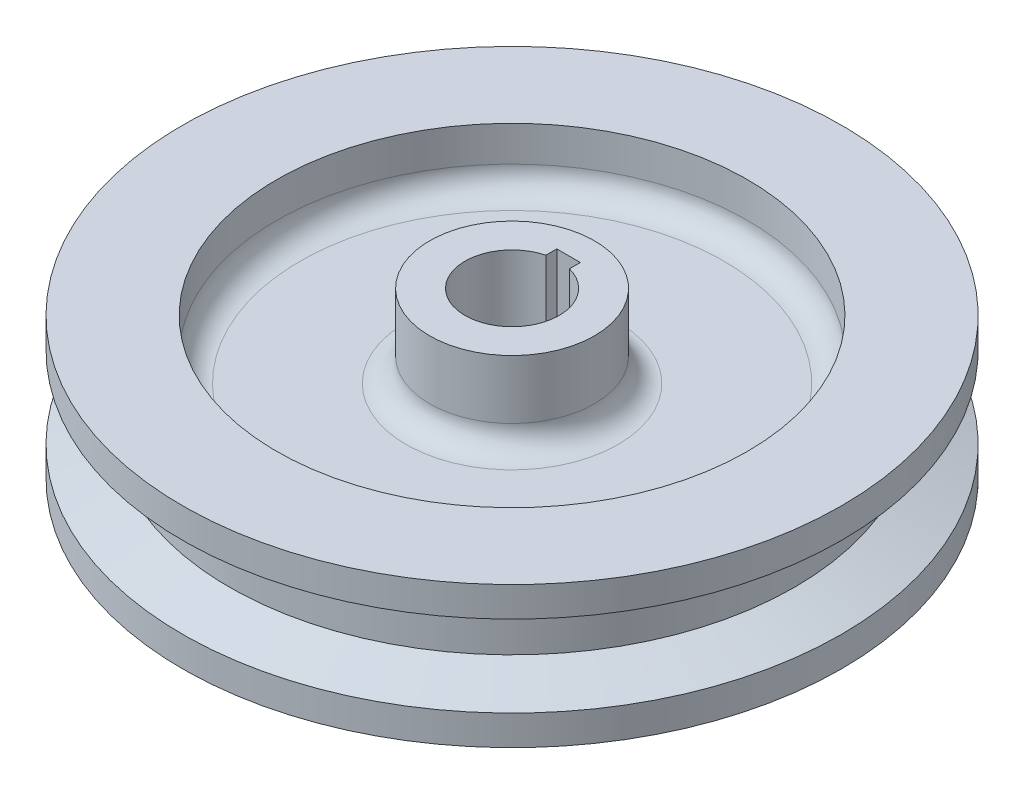
SolidWorks part; units mm, degrees
material "Cast Stainless Steel"
ref_plane "Front Plane" through (0, 0, 0) normal (0, 0, 1) x (1, 0, 0)
ref_plane "Top Plane" through (0, 0, 0) normal (0, 1, 0) x (1, 0, 0)
ref_plane "Right Plane" through (0, 0, 0) normal (1, 0, 0) x (0, 0, -1)
sketch "Sketch1" plane through (0, 0, 0) normal (0, 0, 1) x (1, 0, 0)
  line L0 (0, -1000) -> (0, 49000) construction
  line L1 (-1000, 0) -> (49000, 0) construction
  line L2 (12.7, 25.4) -> (22.225, 25.4)
  line L3 (22.225, 25.4) -> (22.225, 9.525)
  line L4 (28.575, 3.175) -> (57.15, 3.175)
  line L5 (63.5, 9.525) -> (63.5, 19.05)
  line L6 (63.5, 19.05) -> (88.9, 19.05)
  line L7 (88.9, 19.05) -> (88.9, 10.9724)
  line L8 (88.9, 10.9724) -> (76.2, 6.35)
  line L9 (76.2, 6.35) -> (76.2, -6.35)
  line L10 (88.9, -10.9724) -> (76.2, -6.35)
  line L11 (88.9, -19.05) -> (88.9, -10.9724)
  line L12 (63.5, -19.05) -> (88.9, -19.05)
  line L13 (63.5, -9.525) -> (63.5, -19.05)
  line L14 (28.575, -3.175) -> (57.15, -3.175)
  line L15 (22.225, -25.4) -> (22.225, -9.525)
  line L16 (12.7, -25.4) -> (22.225, -25.4)
  line L17 (12.7, 25.4) -> (12.7, -25.4)
  arc A0 (63.5, 9.525) -> (57.15, 3.175) centre (57.15, 9.525) cw
  arc A1 (28.575, 3.175) -> (22.225, 9.525) centre (28.575, 9.525) cw
  arc A2 (28.575, -3.175) -> (22.225, -9.525) centre (28.575, -9.525) ccw
  arc A3 (63.5, -9.525) -> (57.15, -3.175) centre (57.15, -9.525) ccw
  point P27 (76.2, 0)
  dimension "D9" = 6.35
  dimension "D1" = 177.8
  dimension "D2" = 44.45
  dimension "D3" = 6.35
  dimension "D4" = 38.1
  dimension "D5" = 50.8
  dimension "D6" = 6.35
  dimension "D7" = 12.7
  dimension "D8" = 20
  dimension "D10" = 127
  dimension "D11" = 25.4
  dimension "D12" = 40
revolve "Revolve1" add sketch "Sketch1" angle 360 about L0
sketch "Sketch2" plane through (0, 25.4, 0) normal (0, 1, 0) x (1, 0, 0)
  line L0 (-201000, 0) -> (249000, 0) construction
  line L1 (3.175, 0) -> (-3.175, 0)
  line L2 (3.175, 0) -> (3.175, 15.24)
  line L3 (3.175, 15.24) -> (-3.175, 15.24)
  line L4 (-3.175, 0) -> (-3.175, 15.24)
  line L5 (3.175, 0) -> (-3.175, 15.24) construction
  line L6 (3.175, 15.24) -> (-3.175, 0) construction
  line L7 (-201000, 0) -> (249000, 0) construction
  point P0 (0, 7.62)
  dimension "D1" = 15.24
  dimension "D2" = 6.35
extrude "Cut-Extrude1" cut sketch "Sketch2" against normal up to surface (50.8 mm away) up to face at (22.225, -25.4, 0)
